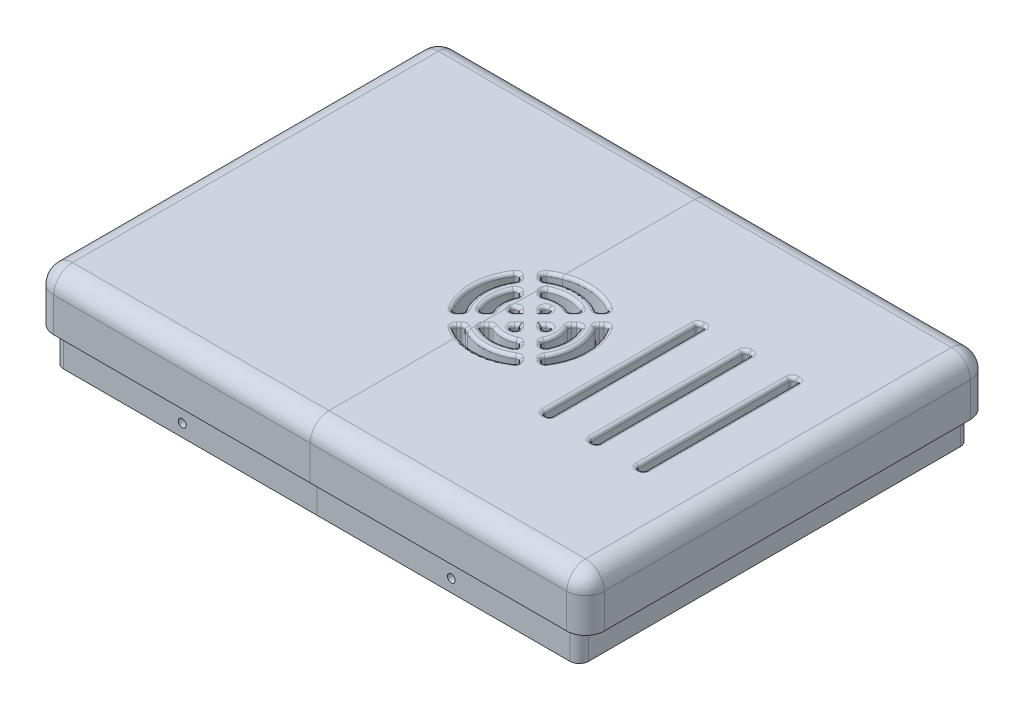
SolidWorks part; units mm, degrees
ref_plane "Plan de face" through (0, 0, 0) normal (0, 0, 1) x (1, 0, 0)
ref_plane "Plan de dessus" through (0, 0, 0) normal (0, 1, 0) x (1, 0, 0)
ref_plane "Plan de droite" through (0, 0, 0) normal (1, 0, 0) x (0, 0, -1)
sketch "Esquisse1" plane through (0, 0, 0) normal (0, 1, 0) x (1, 0, 0)
  line L1 (-88, 64.5) -> (88, 64.5)
  line L2 (-88, 64.5) -> (-88, -64.5)
  line L3 (-88, -64.5) -> (88, -64.5)
  line L4 (88, 64.5) -> (88, -64.5)
  line L5 (-88, 64.5) -> (88, -64.5) construction
  line L6 (-88, -64.5) -> (88, 64.5) construction
  point P0 (0, 0)
  dimension "D1" = 129
  dimension "D2" = 176
extrude "General shape" add sketch "Esquisse1" along normal blind 7
sketch "Esquisse2" plane through (0, 0, 0) normal (0, -1, 0) x (1, 0, 0)
  line L1 (88, -64.5) -> (-88, -64.5)
  line L2 (88, -64.5) -> (88, 64.5)
  line L3 (88, 64.5) -> (-88, 64.5)
  line L4 (-88, -64.5) -> (-88, 64.5)
  line L5 (88, -64.5) -> (-88, 64.5) construction
  line L6 (88, 64.5) -> (-88, -64.5) construction
  line L7 (80, -60) -> (-80, -60)
  line L8 (80, -60) -> (80, 60)
  line L9 (80, 60) -> (-80, 60)
  line L10 (-80, -60) -> (-80, 60)
  line L11 (80, -60) -> (-80, 60) construction
  line L12 (80, 60) -> (-80, -60) construction
  point P0 (0, 0)
  point P7 (0, 0)
  dimension "D1" = 8
  dimension "D2" = 4.5
extrude "Boss.-Extru.2" add sketch "Esquisse2" along normal blind 20
sketch "Esquisse3" plane through (0, -20, 0) normal (0, -1, 0) x (-1, 0, 0)
  line L1 (-88, 64.5) -> (88, 64.5)
  line L2 (-88, 64.5) -> (-88, -64.5)
  line L3 (-88, -64.5) -> (88, -64.5)
  line L4 (88, 64.5) -> (88, -64.5)
  line L5 (-88, 64.5) -> (88, -64.5) construction
  line L6 (-88, -64.5) -> (88, 64.5) construction
  line L7 (-83.9, 62.4) -> (83.9, 62.4)
  line L8 (-83.9, 62.4) -> (-83.9, -62.4)
  line L9 (-83.9, -62.4) -> (83.9, -62.4)
  line L10 (83.9, 62.4) -> (83.9, -62.4)
  line L11 (-83.9, 62.4) -> (83.9, -62.4) construction
  line L12 (-83.9, -62.4) -> (83.9, 62.4) construction
  point P0 (0, 0)
  point P7 (0, 0)
  dimension "D1" = 2.1
  dimension "D2" = 4.1
extrude "Enlèv. mat.-Extru.1" cut sketch "Esquisse3" against normal blind 10
fillet "Fillet1" radius 6 4 edges at (88, -1.5, 64.5) (88, -1.5, -64.5) (-88, -1.5, -64.5) (-88, -1.5, 64.5)
fillet "Fillet2" radius 6 8 edges at (-86.2426, 7, 62.7426) (-88, 7, 0) (-86.2426, 7, -62.7426) (0, 7, -64.5) (86.2426, 7, -62.7426) (88, 7, 0) (86.2426, 7, 62.7426) (0, 7, 64.5)
fillet "Fillet3" radius 3 4 edges at (80, 0, 0) (0, 0, -60) (-80, 0, 0) (0, 0, 60)
fillet "Fillet4" radius 3 4 edges at (-83.9, -15, 62.4) (83.9, -15, 62.4) (83.9, -15, -62.4) (-83.9, -15, -62.4)
sketch "Esquisse4" plane through (0, 0, 0) normal (0, -1, 0) x (1, 0, 0)
  line L0 (6.5, 0.67) -> (-6.2279, 13.3979) construction
  line L1 (-73, -51) -> (73, -51)
  line L2 (-73, -51) -> (-73, 51)
  line L3 (-73, 51) -> (73, 51)
  line L4 (73, -51) -> (73, 51)
  line L5 (-73, -51) -> (73, 51) construction
  line L6 (-73, 51) -> (73, -51) construction
  line L7 (-2.5, 0.67) -> (-5.5, 0.67) construction
  line L8 (-5.5, 0.67) -> (-8.5, 0.67) construction
  line L9 (-8.5, 0.67) -> (-11.5, 0.67) construction
  line L10 (-2.5, 0.67) -> (0.5, 0.67) construction
  line L11 (0.5, 0.67) -> (3.5, 0.67) construction
  line L12 (3.5, 0.67) -> (6.5, 0.67) construction
  line L13 (6.5, 0.67) -> (19.2279, 13.3979) construction
  line L14 (6.5, 0.67) -> (19.2279, -12.0579) construction
  line L15 (6.5, 0.67) -> (-6.2279, -12.0579) construction
  line L16 (25.9454, -22.311) -> (-16.481, 20.1154)
  line L17 (25.9454, -22.311) -> (29.481, -18.7754)
  line L18 (-16.481, 20.1154) -> (-12.9454, 23.651)
  line L19 (29.481, -18.7754) -> (-12.9454, 23.651)
  line L20 (25.9454, -22.311) -> (-12.9454, 23.651) construction
  line L21 (-16.481, 20.1154) -> (29.481, -18.7754) construction
  line L22 (-12.9454, -22.311) -> (29.481, 20.1154)
  line L23 (-12.9454, -22.311) -> (-16.481, -18.7754)
  line L24 (29.481, 20.1154) -> (25.9454, 23.651)
  line L25 (-16.481, -18.7754) -> (25.9454, 23.651)
  line L26 (-12.9454, -22.311) -> (25.9454, 23.651) construction
  line L27 (29.481, 20.1154) -> (-16.481, -18.7754) construction
  circle A0 centre (6.5, 0.67) radius 18
  circle A1 centre (6.5, 0.67) radius 15
  circle A2 centre (6.5, 0.67) radius 12
  circle A3 centre (6.5, 0.67) radius 9
  circle A4 centre (6.5, 0.67) radius 6
  circle A5 centre (6.5, 0.67) radius 3
  point P0 (0, 0)
  point P6 (6.5, 0.67)
  dimension "D1" = 102
  dimension "D2" = 146
  dimension "D3" = 66.5
  dimension "D4" = 51.67
  dimension "D5" = 3
  dimension "D6" = 5
extrude "Fan_extrusion" cut sketch "Esquisse4" against normal up to surface (7 mm away) contours L16 A4 L25 | A3 L16 A2 L25 | A1 L16 A0 L25 | A1 L22 A0 L16 | A3 L22 A2 L16 | L22 A4 L16 | A1 L19 A0 L22 | A3 L19 A2 L22 | L19 A4 L22 | L25 A4 L19 | A3 L25 A2 L19 | A1 L25 A0 L19 region at (6.5, 0, -14.7998) region at (21.9698, 0, 0.67) region at (6.5, 0, -9.4114) region at (-8.9698, 0, 0.67) region at (16.5814, 0, 0.67) region at (6.5, 0, -4.4228) region at (-3.5814, 0, 0.67) region at (6.5, 0, 16.1398) region at (11.5928, 0, 0.67) region at (1.4072, 0, 0.67) region at (6.5, 0, 10.7514) region at (6.5, 0, 5.7628) up to face at (0, 7, 0)
sketch "Esquisse5" plane through (0, 0, 0) normal (0, -1, 0) x (1, 0, 0)
  line L0 (6.5, 6.67) -> (6.5, -5.33) construction
  line L2 (22.55, -15.38) -> (-9.55, -15.38)
  line L3 (22.55, -15.38) -> (22.55, 16.72)
  line L4 (22.55, 16.72) -> (-9.55, 16.72)
  line L5 (-9.55, -15.38) -> (-9.55, 16.72)
  line L6 (22.55, -15.38) -> (-9.55, 16.72) construction
  line L7 (22.55, 16.72) -> (-9.55, -15.38) construction
  arc A0 (8.589, 6.2946) -> (4.411, 6.2946) centre (6.5, 0.67) ccw construction
  arc A1 (4.411, -4.9546) -> (8.589, -4.9546) centre (6.5, 0.67) ccw construction
  circle A3 centre (-9.55, 16.72) radius 1.25
  circle A4 centre (22.55, 16.72) radius 1.25
  circle A5 centre (22.55, -15.38) radius 1.25
  circle A6 centre (-9.55, -15.38) radius 1.25
  point P9 (6.5, 0.67)
  dimension "D3" = 2.5
  dimension "D1" = 32.1
  dimension "D2" = 32.1
extrude "Fan_scree_holes" cut sketch "Esquisse5" against normal blind 5 contours A3 | A6 | A4 | A5
fillet "Fan_fillet" radius 1 126 edges at (19.7992, 7, -9.0936) (19.7992, 7, 10.4336) (19.7992, 0, 10.4336) (19.7992, 0, -9.0936) (15.4741, 7, -4.7685) (15.4741, 7, 6.1085) (15.4741, 0, 6.1085) (15.4741, 0, -4.7685) (-3.2636, 7, -12.6292) (16.2636, 7, -12.6292) (16.2636, 0, -12.6292) (-3.2636, 0, -12.6292) (1.0615, 7, -8.3041) (11.9385, 7, -8.3041) (11.9385, 0, -8.3041) (1.0615, 0, -8.3041) (11.0801, 7, 1.7145) (11.0801, 0, 1.7145) (11.0801, 0, -0.3745) (5.4555, 7, -3.9101) (7.5445, 7, -3.9101) (7.5445, 0, -3.9101) (5.4555, 0, -3.9101) (-6.7992, 7, 10.4336) (-6.7992, 7, -9.0936) (-6.7992, 0, -9.0936) (-6.7992, 0, 10.4336) (-2.4741, 7, 6.1085) (-2.4741, 7, -4.7685) (-2.4741, 0, -4.7685) (-2.4741, 0, 6.1085) (1.9199, 7, 1.7145) (1.9199, 7, -0.3745) (1.9199, 0, -0.3745) (1.9199, 0, 1.7145) (7.5445, 7, 5.2501) (5.4555, 7, 5.2501) (5.4555, 0, 5.2501) (7.5445, 0, 5.2501) (11.9385, 7, 9.6441) (1.0615, 7, 9.6441) (11.9385, 0, 9.6441) (16.2636, 7, 13.9692) (-3.2636, 7, 13.9692) (-3.2636, 0, 13.9692) (16.2636, 0, 13.9692) (14.3813, 3.5, -3.6757) (15.5, 0, 0.67) (14.3813, 3.5, 5.0157) (15.5, 7, 0.67) (18.726, 3.5, -8.0205) (21.5, 0, 0.67) (18.726, 3.5, 9.3605) (21.5, 7, 0.67) (2.1543, 3.5, -7.2113) (6.5, 0, -8.33) (10.8457, 3.5, -7.2113) (6.5, 7, -8.33) (-2.1905, 3.5, -11.556) (6.5, 0, -14.33) (15.1905, 3.5, -11.556) (6.5, 7, -14.33) (24.5, 7, 0.67) (20.8723, 3.5, 11.5068) (24.5, 0, 0.67) (20.8723, 3.5, -10.1668) (18.5, 7, 0.67) (16.5669, 3.5, 7.2013) (18.5, 0, 0.67) (16.5669, 3.5, -5.8613) (6.5, 7, -17.33) (17.3368, 3.5, -13.7023) (6.5, 0, -17.33) (-4.3368, 3.5, -13.7023) (6.5, 7, -11.33) (13.0313, 3.5, -9.3969) (6.5, 0, -11.33) (-0.0313, 3.5, -9.3969) (12.5, 7, 0.67) (12.1246, 3.5, 2.759) (12.5, 0, 0.67) (12.1246, 3.5, -1.419) (6.5, 7, -5.33) (8.589, 3.5, -4.9546) (6.5, 0, -5.33) (4.411, 3.5, -4.9546) (-5.726, 3.5, 9.3605) (-8.5, 0, 0.67) (-5.726, 3.5, -8.0205) (-8.5, 7, 0.67) (-1.3813, 3.5, 5.0157) (-2.5, 0, 0.67) (-1.3813, 3.5, -3.6757) (-2.5, 7, 0.67) (-11.5, 7, 0.67) (-7.8723, 3.5, -10.1668) (-11.5, 0, 0.67) (-7.8723, 3.5, 11.5068) (-5.5, 7, 0.67) (-3.5669, 3.5, -5.8613) (-5.5, 0, 0.67) (-3.5669, 3.5, 7.2013) (0.5, 7, 0.67) (0.8754, 3.5, -1.419) (0.5, 0, 0.67) (0.8754, 3.5, 2.759) (6.5, 7, 6.67) (4.411, 3.5, 6.2946) (6.5, 0, 6.67) (8.589, 3.5, 6.2946) (15.1905, 3.5, 12.896) (6.5, 0, 15.67) (-2.1905, 3.5, 12.896) (6.5, 7, 15.67) (10.8457, 3.5, 8.5513) (6.5, 0, 9.67) (2.1543, 3.5, 8.5513) (6.5, 7, 9.67) (6.5, 7, 12.67) (-0.0313, 3.5, 10.7369) (6.5, 0, 12.67) (13.0313, 3.5, 10.7369) (6.5, 7, 18.67) (-4.3368, 3.5, 15.0423) (6.5, 0, 18.67) (17.3368, 3.5, 15.0423)
sketch "Esquisse8" plane through (0, 7, 0) normal (0, 1, 0) x (1, 0, 0)
  line L0 (-82, 0) -> (82, 0) construction
  line L1 (-82, 58.5) -> (-82, -58.5) construction
  line L2 (82, -58.5) -> (82, 58.5) construction
  line L3 (49.5, -25) -> (52, -25)
  line L10 (64.5, -25) -> (67, -25)
  line L11 (64.5, -25) -> (64.5, 25)
  line L12 (64.5, 25) -> (67, 25)
  line L13 (67, -25) -> (67, 25)
  line L14 (64.5, -25) -> (67, 25) construction
  line L15 (64.5, 25) -> (67, -25) construction
  line L16 (49.5, -25) -> (49.5, 25)
  line L17 (52, -25) -> (52, 25)
  line L18 (49.5, 25) -> (52, 25)
  line L19 (34.5, -25) -> (37, -25)
  line L20 (34.5, -25) -> (34.5, 25)
  line L21 (37, -25) -> (37, 25)
  line L22 (34.5, 25) -> (37, 25)
  point P11 (65.75, 0)
  dimension "D4" = 50
  dimension "D5" = 2.5
  dimension "D6" = 15
  dimension "D7" = 3
extrude "Passive_air_extrusion" cut sketch "Esquisse8" against normal up to surface (7 mm away) up to face at (11.3437, 0, 0.67)
fillet "Passive_air_extrusion_fillet" radius 1 36 edges at (35.75, 0, 25) (35.75, 7, 25) (65.75, 7, 25) (65.75, 0, 25) (64.5, 3.5, 25) (64.5, 7, 0) (64.5, 0, 0) (50.75, 7, 25) (50.75, 0, 25) (49.5, 3.5, 25) (49.5, 7, 0) (49.5, 0, 0) (67, 7, 0) (67, 3.5, 25) (67, 0, 0) (64.5, 3.5, -25) (65.75, 7, -25) (67, 3.5, -25) (65.75, 0, -25) (52, 7, 0) (52, 3.5, 25) (52, 0, 0) (49.5, 3.5, -25) (50.75, 7, -25) (52, 3.5, -25) (50.75, 0, -25) (37, 7, 0) (37, 3.5, 25) (37, 0, 0) (35.75, 7, -25) (37, 3.5, -25) (35.75, 0, -25) (34.5, 3.5, 25) (34.5, 7, 0) (34.5, 3.5, -25) (34.5, 0, 0)
ref_plane "Plane" through (0, 0, 0) normal (1, 0, 0) x (0, 0, -1)
split "Middle_split" trim tools "Plane" bodies to split 109 resulting bodies 112 113
sketch "Esquisse9" plane through (0, 0, 62.4) normal (0, 0, 1) x (1, 0, 0)
  circle A0 centre (-43, -16) radius 1.25
  circle A1 centre (43, -16) radius 1.25
  dimension "D1" = 2.5
extrude "Closing_screw_holes" cut sketch "Esquisse9" against normal through all
